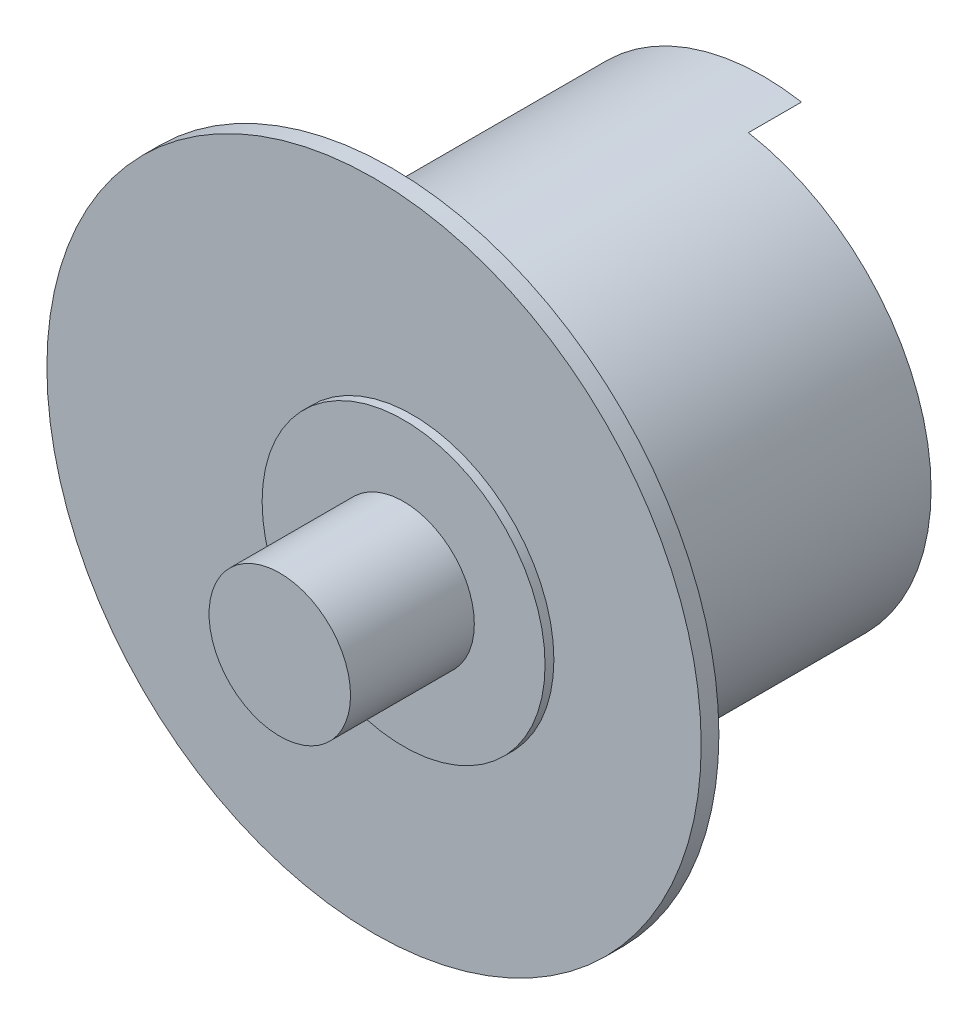
SolidWorks part; units mm, degrees
material "PETG"
ref_plane "Front Plane" through (0, 0, 0) normal (0, 0, 1) x (1, 0, 0)
ref_plane "Top Plane" through (0, 0, 0) normal (0, 1, 0) x (1, 0, 0)
ref_plane "Right Plane" through (0, 0, 0) normal (1, 0, 0) x (0, 0, -1)
sketch "Sketch1" plane through (0, 0, 0) normal (0, 0, 1) x (1, 0, 0)
  line L1 (-2, 3.4641) -> (-4, 0)
  line L2 (-4, 0) -> (-2, -3.4641)
  line L3 (-2, -3.4641) -> (2, -3.4641)
  line L4 (2, -3.4641) -> (4, 0)
  line L5 (4, 0) -> (2, 3.4641)
  line L6 (2, 3.4641) -> (-2, 3.4641)
  circle A0 centre (0, 0) radius 4 construction
  circle A1 centre (-2.17, 0) radius 12.5
  circle A2 centre (0, 0) radius 3.4641 construction
  dimension "D1" = 25
  dimension "D2" = 8
  dimension "D3" = 2.17
extrude "Boss-Extrude1" add sketch "Sketch1" along normal blind 13 contours L1 A0 | A1 region at (0, 0, 0)
sketch "Sketch6" plane through (0, 0, 13) normal (0, 0, 1) x (1, 0, 0)
  circle A0 centre (-2.17, 0) radius 12.5
  circle A1 centre (-2.17, 0) radius 12.5 construction
extrude "Boss-Extrude7" add sketch "Sketch6" along normal blind 5
sketch "Sketch3" plane through (0, 0, 18) normal (0, 0, -1) x (-1, 0, 0)
  circle A0 centre (2.17, 0) radius 18.5
  circle A2 centre (2.17, 0) radius 12.5 construction
  dimension "D1" = 37
extrude "Boss-Extrude3" add sketch "Sketch3" against normal blind 1 contours A0 | A0 region at (-2.17, 0, 18)
sketch "Sketch4" plane through (0, 0, 19) normal (0, 0, 1) x (1, 0, 0)
  circle A0 centre (0, 0) radius 8
  dimension "D1" = 16
extrude "Boss-Extrude5" add sketch "Sketch4" along normal blind 0.5
sketch "Sketch5" plane through (0, 0, 19.5) normal (0, 0, 1) x (1, 0, 0)
  circle A0 centre (0, 0) radius 4
  dimension "D1" = 8
extrude "Boss-Extrude6" add sketch "Sketch5" along normal blind 7
sketch "Sketch7" plane through (0, 0, 0) normal (0, 0, -1) x (-1, 0, 0)
  line L0 (0, 12.3102) -> (0, -12.3102) construction
  line L1 (-2.17, 0) -> (2.17, 0) construction
  circle A0 centre (-2.17, 0) radius 12.5 construction
  circle A1 centre (2.17, 0) radius 12.5 construction
  circle A2 centre (2.17, 0) radius 12.5
  arc A3 (0, 12.3102) -> (0, -12.3102) centre (-2.17, 0) cw
extrude "Boss-Extrude8" add sketch "Sketch7" along normal blind 3 contours A2 A3 region at (-10.0188, -9.3533, 0)
equation "\"N\"= 21"
equation "\"R\"= 65mm"
equation "\"E\" = ROUND(\"R\" / \"N\" * 0.7, 2)"
equation "\"D3@Sketch1\"=\"E\""
